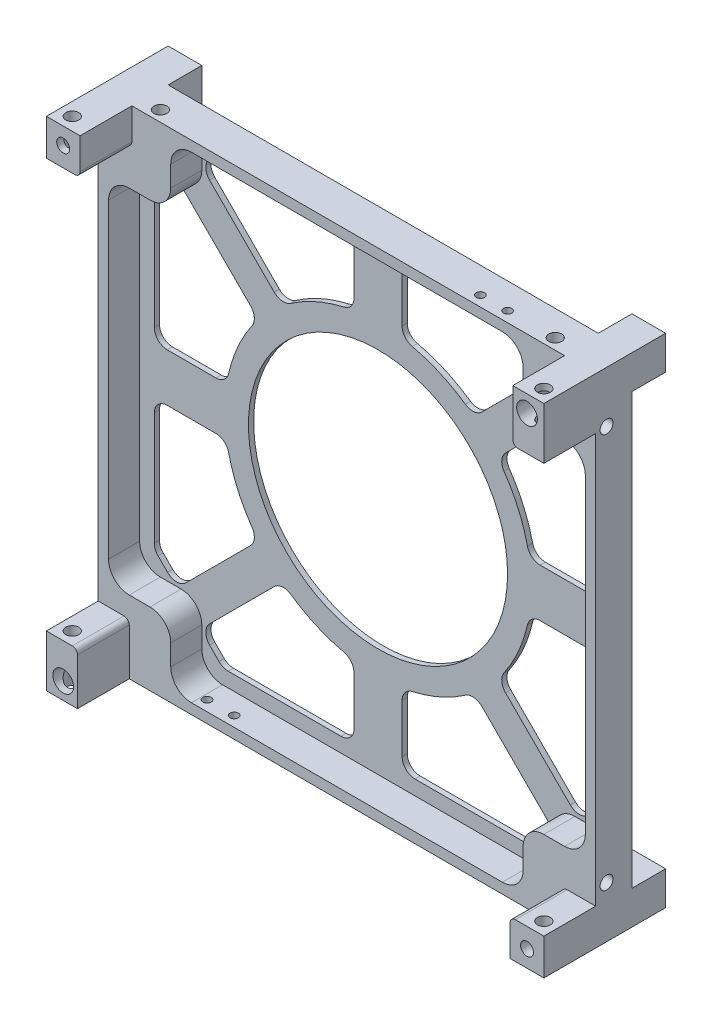
SolidWorks part; units mm, degrees
material "7075-T6 (SN)"
ref_plane "Front Plane" through (0, 0, 0) normal (0, 0, 1) x (1, 0, 0)
ref_plane "Top Plane" through (0, 0, 0) normal (0, 1, 0) x (1, 0, 0)
ref_plane "Right Plane" through (0, 0, 0) normal (1, 0, 0) x (0, 0, -1)
sketch "Sketch1" plane through (0, 0, 0) normal (0, 0, 1) x (1, 0, 0)
  line L0 (0, 0) -> (0, 62.6225) construction
  line L1 (-48, 48) -> (48, 48) construction
  line L2 (-48, 48) -> (-48, -48) construction
  line L3 (-48, -48) -> (48, -48) construction
  line L4 (48, 48) -> (48, -48) construction
  line L5 (0, 0) -> (75.6556, 0) construction
  point P4 (0, 48)
  point P5 (-48, 0)
  dimension "D1" = 96
  dimension "D2" = 96
sketch "Sketch2" plane through (0, 0, 0) normal (0, 0, 1) x (1, 0, 0)
  line L1 (48, 48) -> (41.5, 48)
  line L2 (48, 48) -> (48, 41.5)
  line L3 (48, 41.5) -> (41.5, 41.5)
  line L4 (41.5, 48) -> (41.5, 41.5)
  line L5 (48, -48) -> (41.5, -48)
  line L6 (48, -48) -> (48, -41.5)
  line L7 (48, -41.5) -> (41.5, -41.5)
  line L8 (41.5, -48) -> (41.5, -41.5)
  line L9 (-48, -48) -> (-41.5, -48)
  line L10 (-48, -48) -> (-48, -41.5)
  line L11 (-48, -41.5) -> (-41.5, -41.5)
  line L12 (-41.5, -48) -> (-41.5, -41.5)
  line L13 (-48, 48) -> (-41.5, 48)
  line L14 (-48, 48) -> (-48, 41.5)
  line L15 (-48, 41.5) -> (-41.5, 41.5)
  line L16 (-41.5, 48) -> (-41.5, 41.5)
  dimension "D1" = 6.5
  dimension "D2" = 6.5
  dimension "D3" = 6.5
  dimension "D4" = 6.5
  dimension "D5" = 6.5
  dimension "D6" = 6.5
  dimension "D7" = 6.5
  dimension "D8" = 6.5
sketch "Sketch3" plane through (0, 0, 0) normal (0, 0, 1) x (1, 0, 0)
  line L0 (48, 48) -> (0, 48)
  line L8 (48, 48) -> (48, -48) construction
  line L9 (48, 0) -> (48, 48)
  line L10 (4.64, 40.68) -> (4.64, 31.2753)
  line L12 (0, 0) -> (48, 48) construction
  line L13 (32.5122, 40.6157) -> (30.6801, 42.4478)
  line L14 (25, 0) -> (48, 0)
  line L15 (0, -200000) -> (0, 200062.6225) construction
  line L17 (-48, 48) -> (48, 48) construction
  line L21 (0, 25) -> (0, 48)
  line L22 (20.0352, 24.6032) -> (32.5122, 37.0801)
  line L23 (24.6032, 20.0352) -> (37.0801, 32.5122)
  line L24 (40.6157, 32.5122) -> (42.4478, 30.6801)
  line L25 (7.14, 43.18) -> (28.9124, 43.18)
  line L26 (43.18, 7.14) -> (43.18, 28.9124)
  line L27 (40.68, 4.64) -> (31.2753, 4.64)
  arc A0 (25, 0) -> (0, 25) centre (0, 0) ccw
  arc A1 (28.838, 6.5836) -> (24.3158, 16.8439) centre (0, 0) ccw
  arc A2 (16.8439, 24.3158) -> (6.5836, 28.838) centre (0, 0) ccw
  arc A3 (7.14, 43.18) -> (4.64, 40.68) centre (7.14, 40.68) ccw
  arc A4 (4.64, 31.2753) -> (6.5836, 28.838) centre (7.14, 31.2753) ccw
  arc A5 (20.0352, 24.6032) -> (16.8439, 24.3158) centre (18.2675, 26.3709) cw
  arc A6 (32.5122, 37.0801) -> (32.5122, 40.6157) centre (30.7445, 38.8479) ccw
  arc A7 (28.9124, 43.18) -> (30.6801, 42.4478) centre (28.9124, 40.68) cw
  arc A8 (31.2753, 4.64) -> (28.838, 6.5836) centre (31.2753, 7.14) cw
  arc A9 (40.68, 4.64) -> (43.18, 7.14) centre (40.68, 7.14) ccw
  arc A10 (43.18, 28.9124) -> (42.4478, 30.6801) centre (40.68, 28.9124) ccw
  arc A11 (24.6032, 20.0352) -> (24.3158, 16.8439) centre (26.3709, 18.2675) ccw
  arc A12 (37.0801, 32.5122) -> (40.6157, 32.5122) centre (38.8479, 30.7445) cw
  point P39 (4.64, 29.2138)
  point P42 (18.5072, 23.0751)
  point P45 (34.28, 38.8479)
  dimension "D1" = 50
  dimension "D2" = 4.58
  dimension "D10" = 2.5
  dimension "D11" = 2.5
  dimension "D3" = 4.64
  dimension "D4" = 4.82
  dimension "D5" = 6.46
  dimension "D6" = 3.23
  dimension "D7" = 4.82
  dimension "D8" = 4.64
  dimension "D9" = 13.72
extrude "Boss-Extrude2" add sketch "Sketch3" along normal blind 1
ref_axis "Axis1" through (0, 0, 7.875) along (0, 0, -1)
pattern_circular "CirPattern3" count 4 over 360 about axis through (0, 0, 7.875) along (0, 0, -1) of "Boss-Extrude2"
extrude "Boss-Extrude3" add sketch "Sketch2" against normal blind 6.5
sketch "Sketch4" plane through (0, 0, 1) normal (0, 0, 1) x (1, 0, 0)
  line L0 (46, -34) -> (46, 34)
  line L1 (34, 46) -> (-34, 46)
  line L2 (-46, 34) -> (-46, -34)
  line L3 (-34, -46) -> (34, -46)
  line L4 (-48, 48) -> (-48, -48)
  line L5 (-48, -48) -> (48, -48)
  line L6 (48, -48) -> (48, 48)
  line L7 (48, 48) -> (-48, 48)
  line L15 (-46, 34) -> (-34, 34)
  line L16 (-34, 46) -> (-34, 34)
  line L19 (46, 34) -> (34, 34)
  line L20 (34, 46) -> (34, 34)
  line L23 (46, -34) -> (34, -34)
  line L24 (34, -46) -> (34, -34)
  line L27 (-46, -34) -> (-34, -34)
  line L28 (-34, -46) -> (-34, -34)
  line L29 (-34, 46) -> (-46, 34) construction
  point P2 (46, -46)
  point P4 (46, 46)
  point P6 (-46, 46)
  point P7 (-46, -46)
  dimension "D3" = 14
  dimension "D4" = 14
  dimension "D5" = 2
  dimension "D6" = 2
  dimension "D1" = 14
  dimension "D2" = 14
  dimension "D7" = 2
  dimension "D8" = 2
extrude "Boss-Extrude4" add sketch "Sketch4" along normal blind 6
sketch "Sketch5" plane through (0, 0, 7) normal (0, 0, 1) x (1, 0, 0)
  line L1 (-48, 48) -> (-41.5, 48)
  line L2 (-48, 48) -> (-48, 41)
  line L3 (-48, 41) -> (-41.5, 41)
  line L4 (-41.5, 48) -> (-41.5, 41)
  line L5 (48, 48) -> (42, 48)
  line L6 (48, 48) -> (48, 38)
  line L7 (48, 38) -> (42, 38)
  line L8 (42, 48) -> (42, 38)
  line L9 (-48, -48) -> (-42, -48)
  line L10 (-48, -48) -> (-48, -38)
  line L11 (-48, -38) -> (-42, -38)
  line L12 (-42, -48) -> (-42, -38)
  line L13 (48, -48) -> (41.5, -48)
  line L14 (48, -48) -> (48, -41)
  line L15 (48, -41) -> (41.5, -41)
  line L16 (41.5, -48) -> (41.5, -41)
  dimension "D1" = 6.5
  dimension "D2" = 7
  dimension "D3" = 6
  dimension "D4" = 10
  dimension "D5" = 6.5
  dimension "D6" = 7
  dimension "D7" = 10
  dimension "D8" = 6
extrude "Boss-Extrude5" add sketch "Sketch5" along normal blind 10
sketch "RailHolePosition" plane through (0, 48, 0) normal (0, 1, 0) x (1, 0, 0)
  line L0 (45.5, 6.5) -> (45.5, -14.5) construction
  line L1 (48, -17) -> (48, 6.5) construction
  line L5 (-45.5, 6.5) -> (-45.5, -14.5) construction
  line L7 (48, 6.5) -> (41.5, 6.5) construction
  line L8 (-48, -17) -> (-48, 6.5) construction
  line L9 (-41.5, 6.5) -> (-48, 6.5) construction
  dimension "D1" = 21
  dimension "D2" = 2.5
  dimension "D3" = 2.5
hole_wizard "M3 Tapped RailHoles" positions "Sketch12" profile "Sketch13" tap size "M3" standard "ISO"
sketch "Sketch12" plane through (0, 48, 0) normal (0, 1, 0) x (1, 0, 0)
  point P8 (45.5, -14.5)
  point P11 (-45.5, -14.5)
sketch "Sketch13" plane through (45.5, 48, 14.5) normal (1, 0, 0) x (0, 0, 1)
  line L0 (0, 0) -> (0, 13.2511)
  line L1 (0, 13.2511) -> (1.25, 12.5)
  line L2 (1.25, 12.5) -> (1.25, 0)
  line L5 (1.25, 0) -> (0, 0)
  line L10 (0, 13.2511) -> (-1.25, 12.5) construction
  line L11 (0, -6.35) -> (0, 107.95) construction
  dimension "Tap Drill Dia." = 2.5
  dimension "Tap Drill Depth" = 12.5
  dimension "Drill Angle" = 118
cosmetic thread "Hole Thread1" parameters "D1"=7, "D2"=3
cosmetic thread "Hole Thread18" parameters "D1"=10, "D2"=3
mirror "RailHoles" about plane through (0, 0, 0) normal (0, 1, 0) of "M3 Tapped RailHoles"
cosmetic thread "Hole Thread19" parameters "D1"=7, "D2"=3
cosmetic thread "Hole Thread20" parameters "D1"=10, "D2"=3
sketch3d "SidePlateHole Positions"
  line L0 (-38.1, -48, 7) -> (-38.1, -48, 0) construction
  line L1 (-42, -48, 7) -> (41.5, -48, 7) construction
  line L2 (-48, -48, 0) -> (48, -48, 0) construction
  line L3 (-38.1, -48, 4.9) -> (-48, -48, 4.9) construction
  line L5 (-48, -48, 17) -> (-48, -48, -6.5) construction
  line L6 (-41.5, -48, 0) -> (41.5, -48, 0) construction
  line L17 (-48, -48, 4.9) -> (-48, -38.1, 4.9) construction
  line L18 (-48, -38.1, 4.9) -> (-48, -38.1, 0) construction
  line L19 (-48, 48, 0) -> (-48, -48, 0) construction
  dimension "D1" = 4.9
  dimension "D2" = 9.9
  dimension "D7" = 9.9
hole_wizard "M3x0.5 Tapped SidePlate" positions "Sketch16" profile "Sketch17" tap size "M3x0.5" standard "ANSI Metric"
sketch "Sketch16" plane through (0, -48, 0) normal (0, -1, 0) x (-1, 0, 0)
  point P0 (38.1, -4.9)
sketch "Sketch17" plane through (-38.1, -48, 4.9) normal (1, 0, 0) x (0, 0, -1)
  line L0 (0, 0) -> (0, 8.2511)
  line L1 (0, 8.2511) -> (1.25, 7.5)
  line L2 (1.25, 7.5) -> (1.25, 0)
  line L5 (1.25, 0) -> (0, 0)
  line L10 (0, 8.2511) -> (-1.25, 7.5) construction
  line L11 (0, -6.35) -> (0, 107.95) construction
  dimension "Tap Drill Dia." = 2.5
  dimension "Tap Drill Depth" = 7.5
  dimension "Drill Angle" = 118
cosmetic thread "Hole Thread3" parameters "D1"=6, "D2"=3
hole_wizard "M3x0.5 Tapped SidePlate2" positions "Sketch18" profile "Sketch19" tap size "M3x0.5" standard "ANSI Metric"
sketch "Sketch18" plane through (-48, 0, 0) normal (-1, 0, 0) x (0, 0, 1)
  point P0 (4.9, -38.1)
sketch "Sketch19" plane through (-48, -38.1, 4.9) normal (0, 1, 0) x (0, 0, 1)
  line L0 (0, 0) -> (0, 8.2511)
  line L1 (0, 8.2511) -> (1.25, 7.5)
  line L2 (1.25, 7.5) -> (1.25, 0)
  line L5 (1.25, 0) -> (0, 0)
  line L10 (0, 8.2511) -> (-1.25, 7.5) construction
  line L11 (0, -6.35) -> (0, 107.95) construction
  dimension "Tap Drill Dia." = 2.5
  dimension "Tap Drill Depth" = 7.5
  dimension "Drill Angle" = 118
cosmetic thread "Hole Thread4" parameters "D1"=6, "D2"=3
pattern_circular "SidePlateHoles" count 4 over 360 about axis through (0, 0, 1) along (0, 0, -1) of "M3x0.5 Tapped SidePlate", "M3x0.5 Tapped SidePlate2"
cosmetic thread "Hole Thread5" parameters "D1"=6, "D2"=3
cosmetic thread "Hole Thread6" parameters "D1"=6, "D2"=3
cosmetic thread "Hole Thread7" parameters "D1"=6, "D2"=3
cosmetic thread "Hole Thread8" parameters "D1"=6, "D2"=3
cosmetic thread "Hole Thread9" parameters "D1"=6, "D2"=3
cosmetic thread "Hole Thread10" parameters "D1"=6, "D2"=3
sketch3d "LimitSwitchHolePositions"
  line L0 (-48, -48, 5) -> (-29, -48, 5) construction
  line L1 (-48, -48, 17) -> (-48, -48, -6.5) construction
  line L2 (-48, -48, 0) -> (48, -48, 0) construction
  line L3 (-29, -48, 5) -> (-23.75, -48, 5) construction
  dimension "D1" = 19
  dimension "D2" = 5
  dimension "D3" = 5.25
hole_wizard "M2x0.4 Tapped Hole1" positions "Sketch20" profile "Sketch21" tap size "M2x0.4" standard "ANSI Metric"
sketch "Sketch20" plane through (0, -48, 0) normal (0, -1, 0) x (-1, 0, 0)
  point P0 (29, -5)
  point P3 (23.75, -5)
sketch "Sketch21" plane through (-29, -48, 5) normal (1, 0, 0) x (0, 0, -1)
  line L0 (0, 0) -> (0, 5.6807)
  line L1 (0, 5.6807) -> (0.8, 5.2)
  line L2 (0.8, 5.2) -> (0.8, 0)
  line L5 (0.8, 0) -> (0, 0)
  line L10 (0, 5.6807) -> (-0.8, 5.2) construction
  line L11 (0, -6.35) -> (0, 107.95) construction
  dimension "Tap Drill Dia." = 1.6
  dimension "Tap Drill Depth" = 5.2
  dimension "Drill Angle" = 118
cosmetic thread "Hole Thread11" parameters "D1"=4, "D2"=2
cosmetic thread "Hole Thread12" parameters "D1"=4, "D2"=2
pattern_circular "LimitSwitchHoles" count 2 over 360 about axis through (0, 0, 1) along (0, 0, -1) of "M2x0.4 Tapped Hole1"
cosmetic thread "Hole Thread13" parameters "D1"=4, "D2"=2
cosmetic thread "Hole Thread14" parameters "D1"=4, "D2"=2
fillet "Fillet2" radius 4 12 edges at (-46, -34, 4) (-34, -34, 4) (-34, -46, 4) (34, -46, 4) (34, -34, 4) (46, -34, 4) (46, 34, 4) (34, 34, 4) (34, 46, 4) (-34, 46, 4) (-34, 34, 4) (-46, 34, 4)
sketch "Sketch22" plane through (0, 0, 17) normal (0, 0, 1) x (1, 0, 0)
  line L0 (44.75, 48) -> (44.75, 44.75) construction
  line L1 (48, 48) -> (42, 48) construction
  line L3 (48, 38) -> (48, 48) construction
  dimension "D1" = 3.25
  dimension "D2" = 3.25
hole_wizard "M3 Tapped Standoff Hole" positions "Sketch23" profile "Sketch25" tap size "M3" standard "ISO" end condition through all
sketch "Sketch23" plane through (0, 0, 17) normal (0, 0, 1) x (1, 0, 0)
  point P0 (44.75, 44.75)
sketch "Sketch25" plane through (44.75, 44.75, 17) normal (1, 0, 0) x (0, -1, 0)
  line L0 (0, 0) -> (0, 23.5)
  line L1 (0, 23.5) -> (1.25, 23.5)
  line L2 (1.25, 23.5) -> (1.25, 0)
  line L5 (1.25, 0) -> (0, 0)
  line L11 (0, -6.35) -> (0, 107.95) construction
  dimension "Thread Major Dia." = 2.5
  dimension "Thru Tap Drill Depth" = 23.5
pattern_circular "StandoffHoles" count 4 over 360 about axis through (0, 0, 1) along (0, 0, -1) of "M3 Tapped Standoff Hole"
sketch "Sketch26" plane through (0, 0, 0) normal (0, 0, -1) x (-1, 0, 0)
  line L0 (0, 0) -> (40, -37.5) construction
  line L1 (0, -200000) -> (0, 200062.6225) construction
  line L2 (200000, 0) -> (-200075.6556, 0) construction
  line L3 (12.925, 0) -> (-12.925, 0) construction
  line L4 (0, 0) -> (40, 37.5) construction
  circle A0 centre (40, -37.5) radius 1.7
  circle A1 centre (40, 37.5) radius 1.7
  dimension "D3" = 3.4
  dimension "D1" = 40
  dimension "D2" = 37.5
extrude "Boss-Extrude6" add sketch "Sketch26" along normal blind 3
sketch "BottomHolePositions" plane through (0, 0, -3) normal (0, 0, -1) x (-1, 0, 0)
  line L0 (41.7, -37.5) -> (40, -37.5) construction
  line L1 (41.7, 37.5) -> (40, 37.5) construction
  circle A0 centre (40, -37.5) radius 1.7 construction
  circle A1 centre (40, 37.5) radius 1.7 construction
hole_wizard "M1.6x0.35 Tapped Hole1" positions "Sketch30" profile "Sketch31" tap size "M1.6x0.35" standard "ANSI Metric"
sketch "Sketch30" plane through (0, 0, -3) normal (0, 0, -1) x (-1, 0, 0)
  point P0 (40, -37.5)
  point P3 (40, 37.5)
sketch "Sketch31" plane through (-40, -37.5, -3) normal (1, 0, 0) x (0, 1, 0)
  line L0 (0, 0) -> (0, 3.3755)
  line L1 (0, 3.3755) -> (0.625, 3)
  line L2 (0.625, 3) -> (0.625, 0)
  line L5 (0.625, 0) -> (0, 0)
  line L10 (0, 3.3755) -> (-0.625, 3) construction
  line L11 (0, -6.35) -> (0, 107.95) construction
  dimension "Tap Drill Dia." = 1.25
  dimension "Tap Drill Depth" = 3
  dimension "Drill Angle" = 118
mirror "BottomHoles" about plane through (0, 0, 0) normal (1, 0, 0) of "Boss-Extrude6", "M1.6x0.35 Tapped Hole1"
hole_wizard "CBORE for M5 Hex Head Bolt1" positions "Sketch33" profile "Sketch34" counterbore size "M5" standard "ISO" end condition through all
sketch "Sketch33" plane through (0, 0, 17) normal (0, 0, 1) x (1, 0, 0)
  point P0 (44.75, 44.75)
sketch "Sketch34" plane through (44.75, 44.75, 17) normal (1, 0, 0) x (0, -1, 0)
  line L0 (0, 0) -> (0, 23.5)
  line L1 (0, 23.5) -> (1, 23.5)
  line L3 (1, 23.5) -> (1, 10)
  line L4 (1, 10) -> (2, 10)
  line L5 (2, 10) -> (2, 0)
  line L7 (2, 0) -> (0, 0)
  line L11 (0, -6.35) -> (0, 107.95) construction
  dimension "Thru Hole Dia." = 2
  dimension "Thru Hole Depth" = 23.5
  dimension "C'Bore Dia." = 4
  dimension "C'Bore Depth" = 10
pattern_circular "CirPattern4" count 2 over 360 about axis through (0, 0, 7.875) along (0, 0, -1) of "CBORE for M5 Hex Head Bolt1"
fillet "Fillet3" radius 1 4 edges at (42, 38, 12) (-41.5, 41, 12) (-42, -38, 12) (41.5, -41, 12)
